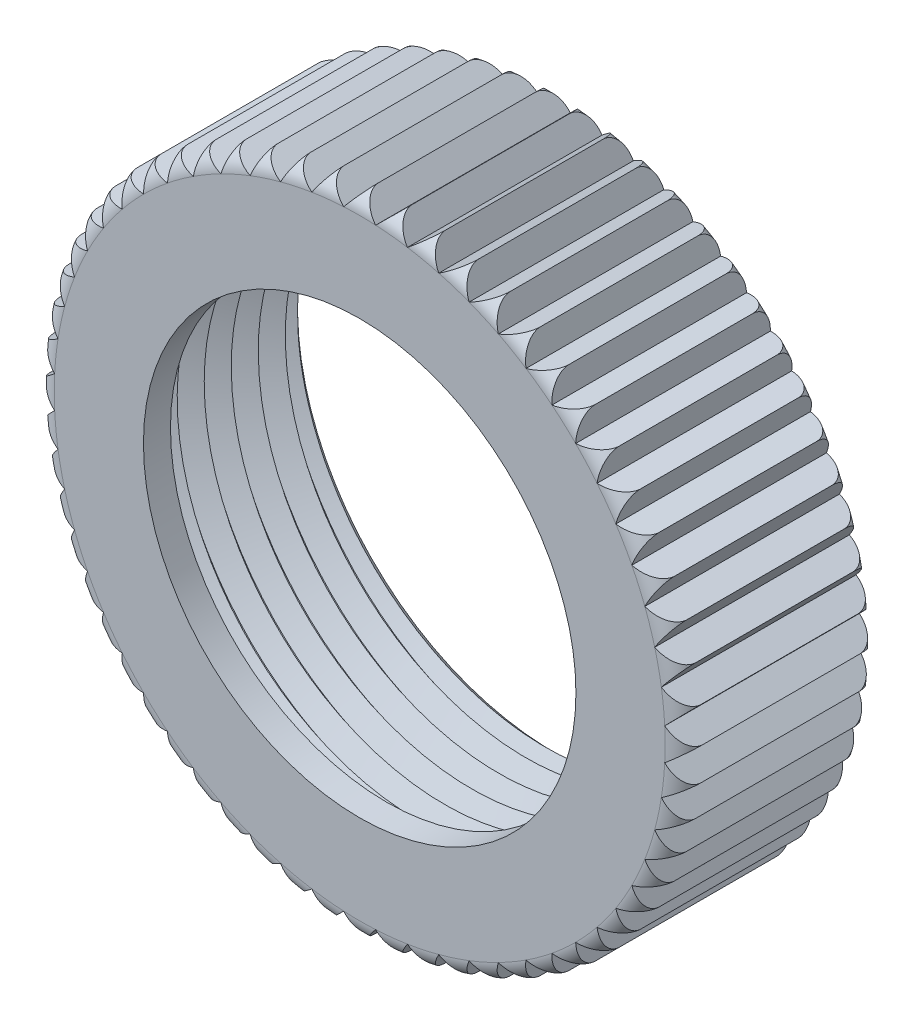
SolidWorks part; units mm, degrees
ref_plane "Front Plane" through (0, 0, 0) normal (0, 0, 1) x (1, 0, 0)
ref_plane "Top Plane" through (0, 0, 0) normal (0, 1, 0) x (1, 0, 0)
ref_plane "Right Plane" through (0, 0, 0) normal (1, 0, 0) x (0, 0, -1)
sketch "Sketch1" plane through (0, 0, 0) normal (0, 0, 1) x (1, 0, 0)
  circle A0 centre (0, 0) radius 4.5
  circle A1 centre (0, 0) radius 6
  dimension "D1" = 12
  dimension "D2" = 9
extrude "Boss-Extrude1" add sketch "Sketch1" along normal blind 3.5 and the other way blind 0.1
chamfer "Chamfer1" distance 0.25 angle 45 2 edges at (4.5, 0, -0.1) (4.5, 0, 3.5)
fillet "Fillet1" radius 0.35 2 edges at (6, 0, 3.5) (6, 0, -0.1)
sketch "Sketch3" plane through (0, 0, -0.1) normal (0, 0, -1) x (-1, 0, 0)
  circle A0 centre (0, 0) radius 4.5 construction
  circle A1 centre (0, 0) radius 4.5
curve "Helix/Spiral1" pitch 0.5 height 5 turns 10
sketch "Sketch4" plane through (0, 0, 0) normal (1, 0, 0) x (0, 0, -1)
  line L0 (0, 4.5) -> (0, 4.75) construction
  line L1 (0.25, 4.5) -> (0.0335, 4.875)
  line L2 (0, 4.5) -> (0.25, 4.5) construction
  line L3 (-0.25, 4.5) -> (-0.0335, 4.875)
  line L4 (0.25, 4.5) -> (0.25, 4.3053)
  line L5 (0.25, 4.3053) -> (-0.25, 4.3053)
  line L6 (0, 4.75) -> (0, 4.875) construction
  line L7 (-0.25, 4.5) -> (-0.25, 4.3053)
  line L8 (0, 4.875) -> (0.0335, 4.875)
  line L9 (0, 4.875) -> (-0.0335, 4.875)
  point P6 (0, 4.3053)
  dimension "D1" = 0.25
  dimension "D2" = 0.25
  dimension "D3" = 0.125
sweep "Cut-Sweep1" cut profiles "Sketch4" path "Helix/Spiral1"
sketch "Sketch5" plane through (0, 0, 3.5) normal (0, 0, 1) x (1, 0, 0)
  circle A0 centre (0, 0) radius 4.875
extrude "Cut-Extrude1" cut sketch "Sketch5" against normal blind 0.5
sketch "Sketch6" plane through (0, 0, 3.5) normal (0, 0, 1) x (1, 0, 0)
  circle A0 centre (0, 0) radius 4.875 construction
  circle A1 centre (0, 0) radius 4.875
extrude "Boss-Extrude2" add sketch "Sketch6" against normal blind 0.5
sketch "Sketch7" plane through (0, 0, 3.5) normal (0, 0, 1) x (1, 0, 0)
  circle A0 centre (0, 0) radius 4
  dimension "D1" = 8
extrude "Cut-Extrude2" cut sketch "Sketch7" against normal blind 1.5
sketch "Sketch8" plane through (0, 0, 3.5) normal (0, 0, 1) x (1, 0, 0)
  line L0 (0, 0) -> (-6, 0) construction
  line L1 (0, 0) -> (-5.9918, 0.314) construction
  line L2 (0, 0) -> (-5.9671, 0.6272) construction
  line L3 (-6, 0) -> (-5.6423, 0.2957)
  line L4 (-5.6423, 0.2957) -> (-5.9671, 0.6272)
  line L5 (-5.9671, 0.6272) -> (-6.331, 0.6272)
  line L6 (-6.331, 0.6272) -> (-6.3104, 0)
  line L7 (-6.3104, 0) -> (-6, 0)
  circle A0 centre (0, 0) radius 6 construction
  circle A1 centre (0, 0) radius 5.65 construction
  dimension "D1" = 3
  dimension "D2" = 3
extrude "Cut-Extrude3" cut sketch "Sketch8" against normal blind 7.5
pattern_circular "CirPattern1" count 60 over 360 about axis through (0, 0, 0) along (0, 0, 1) of "Cut-Extrude3"
